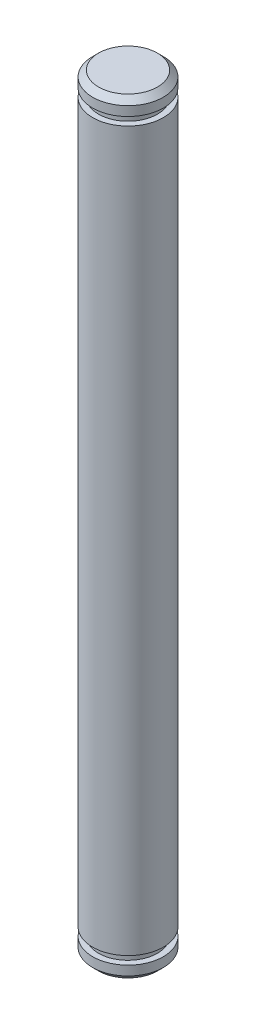
SolidWorks part; units mm, degrees
ref_plane "Front Plane" through (0, 0, 0) normal (0, 0, 1) x (1, 0, 0)
ref_plane "Top Plane" through (0, 0, 0) normal (0, 1, 0) x (1, 0, 0)
ref_plane "Right Plane" through (0, 0, 0) normal (1, 0, 0) x (0, 0, -1)
sketch "Sketch1" plane through (0, 0, 0) normal (0, 1, 0) x (1, 0, 0)
  circle A0 centre (0, 0) radius 3
  dimension "D1" = 6
extrude "50" add sketch "Sketch1" along normal blind 65
sketch "Sketch2" plane through (0, 65, 0) normal (0, 1, 0) x (1, 0, 0)
  circle A0 centre (0, 0) radius 2.5
  circle A1 centre (0, 0) radius 3 construction
  circle A2 centre (0, 0) radius 3
  dimension "D1" = 5
extrude "Cut-Extrude1" cut sketch "Sketch2" along normal blind 0.7 from offset 2 offset against normal yes
sketch "Sketch3" plane through (0, 0, 0) normal (0, -1, 0) x (1, 0, 0)
  circle A0 centre (0, 0) radius 3 construction
  circle A1 centre (0, 0) radius 2.5 construction
  circle A2 centre (0, 0) radius 3
  circle A3 centre (0, 0) radius 2.5
extrude "Cut-Extrude2" cut sketch "Sketch3" along normal blind 0.7 from offset 2 offset against normal yes
chamfer "Chamfer1" distance 0.5 angle 45 2 edges at (0, 65, 3) (0, 0, 3)
